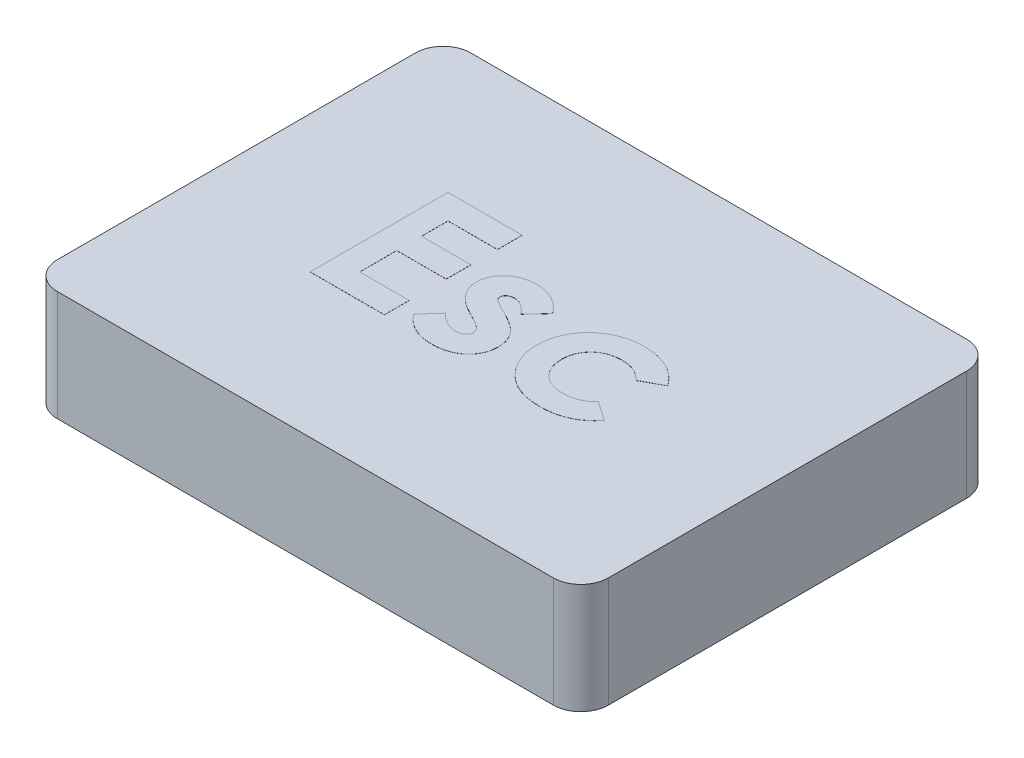
SolidWorks part; units mm, degrees
ref_plane "Front Plane" through (0, 0, 0) normal (0, 0, 1) x (1, 0, 0)
ref_plane "Top Plane" through (0, 0, 0) normal (0, 1, 0) x (1, 0, 0)
ref_plane "Right Plane" through (0, 0, 0) normal (1, 0, 0) x (0, 0, -1)
sketch "Sketch1" plane through (0, 0, 0) normal (0, 1, 0) x (1, 0, 0)
  line L0 (0, 0) -> (12.7, 0)
  line L1 (12.7, 0) -> (12.7, 9.525)
  line L2 (12.7, 9.525) -> (0, 9.525)
  line L3 (0, 9.525) -> (0, 0)
  dimension "D1" = 12.7
  dimension "D2" = 9.525
extrude "Boss-Extrude1" add sketch "Sketch1" along normal blind 2.54
fillet "Fillet1" radius 0.635 4 edges at (0, 1.27, -9.525) (12.7, 1.27, -9.525) (12.7, 1.27, 0) (0, 1.27, 0)
shell "Shell1" thickness 0.635 removed face at (6.35, 0, -4.7625)
sketch "Sketch2" plane through (0, 1.905, 0) normal (0, -1, 0) x (-1, 0, 0)
  line L0 (-0.635, 4.7625) -> (-12.065, 4.7625) construction
  line L1 (-0.635, 8.89) -> (-0.635, 0.635) construction
  line L2 (-12.065, 0.635) -> (-12.065, 8.89) construction
  line L3 (-6.35, 0.635) -> (-6.35, 8.89) construction
  line L4 (-0.635, 0.635) -> (-12.065, 0.635) construction
  line L5 (-12.065, 8.89) -> (-0.635, 8.89) construction
  circle A0 centre (-6.35, 4.7625) radius 2.54
  dimension "D1" = 5.08
extrude "Boss-Extrude2" add sketch "Sketch2" along normal up to surface (1.905 mm away) up to face at (6.35, 0, -4.7625)
sketch "Sketch3" plane through (0, 2.54, 0) normal (0, 1, 0) x (1, 0, 0)
  line L0 (0.635, 0) -> (12.065, 0) construction
  line L1 (0, 8.89) -> (0, 0.635) construction
  text T0 "<b>Esc</b>"
  dimension "D1" = 3.302
  dimension "D2" = 2.794
extrude "Boss-Extrude3" add sketch "Sketch3" along normal blind 0.0025
